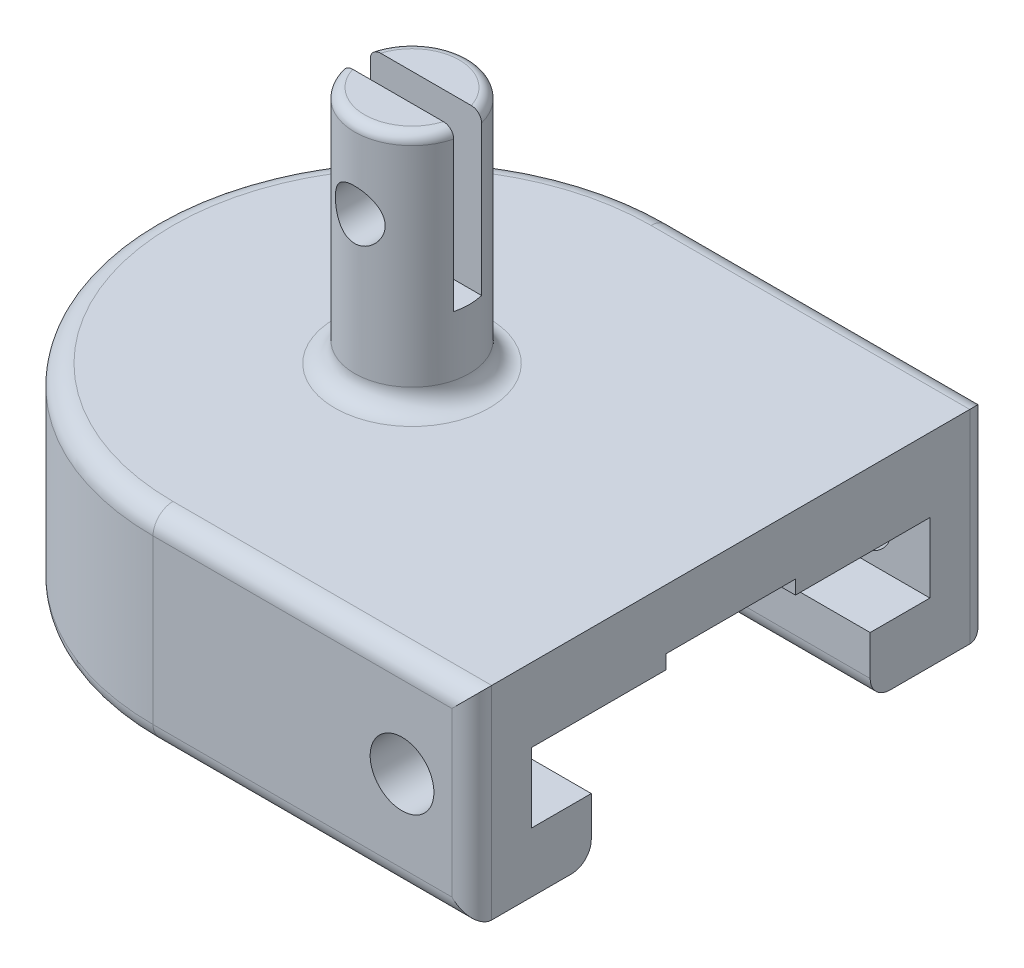
SolidWorks part; units mm, degrees
material "ABS"
ref_plane "Front Plane" through (0, 0, 0) normal (0, 0, 1) x (1, 0, 0)
ref_plane "Top Plane" through (0, 0, 0) normal (0, 1, 0) x (1, 0, 0)
ref_plane "Right Plane" through (0, 0, 0) normal (1, 0, 0) x (0, 0, -1)
sketch "Sketch1" plane through (0, 0, 0) normal (0, 1, 0) x (1, 0, 0)
  line L0 (0, 13) -> (16, 13)
  line L1 (0, -13) -> (16, -13)
  line L2 (0, 7) -> (16, 7)
  line L3 (16, 13) -> (16, 7)
  line L4 (0, -7) -> (16, -7)
  line L5 (16, -7) -> (16, -13)
  arc A0 (0, 7) -> (0, -7) centre (0, 0) ccw
  arc A1 (0, 13) -> (0, -13) centre (0, 0) ccw
  dimension "D1" = 6
  dimension "D2" = 7
  dimension "D3" = 16
  dimension "D4" = 16
extrude "Boss-Extrude1" add sketch "Sketch1" along normal blind 3
sketch "Sketch2" plane through (0, 3, 0) normal (0, 1, 0) x (1, 0, 0)
  line L0 (0, 13) -> (16, 13)
  line L1 (16, 13) -> (16, 10)
  line L2 (16, 7) -> (16, 13) construction
  line L3 (16, -13) -> (0, -13)
  line L4 (16, -13) -> (16, -10)
  line L7 (16, -13) -> (16, -7) construction
  line L8 (0, 10) -> (16, 10)
  line L9 (0, -10) -> (16, -10)
  arc A0 (0, 10) -> (0, -10) centre (0, 0) ccw
  arc A1 (0, 13) -> (0, -13) centre (0, 0) ccw
  dimension "D2" = 3
extrude "Boss-Extrude2" add sketch "Sketch2" along normal blind 3.5
sketch "Sketch3" plane through (0, 6.5, 0) normal (0, 1, 0) x (1, 0, 0)
  line L0 (16, 13) -> (0, 13)
  line L1 (16, 13) -> (16, 7)
  line L3 (0, -13) -> (16, -13)
  line L4 (16, -13) -> (16, -7)
  line L5 (16, -7) -> (0, -7) construction
  line L6 (16, -10) -> (16, -7) construction
  line L8 (16, 7) -> (16, -7)
  arc A1 (0, 13) -> (0, -13) centre (0, 0) ccw
extrude "Boss-Extrude3" add sketch "Sketch3" along normal blind 3.7
sketch "Sketch4" plane through (0, 10.2, 0) normal (0, 1, 0) x (1, 0, 0)
  circle A0 centre (0, 0) radius 2.88
  dimension "D1" = 5.76
extrude "Boss-Extrude4" add sketch "Sketch4" along normal blind 12
sketch "Sketch11" plane through (16, 0, 0) normal (1, 0, 0) x (0, 0, -1)
  line L5 (-10, 6.5) -> (10, 6.5) construction
  line L6 (-3.25, 6.5) -> (3.25, 6.5)
  line L7 (-3.25, 6.5) -> (-3.25, 7.2)
  line L8 (-3.25, 7.2) -> (3.25, 7.2)
  line L9 (3.25, 6.5) -> (3.25, 7.2)
  line L10 (0, 10.2) -> (0, 6.5) construction
  line L11 (-13, 10.2) -> (13, 10.2) construction
  line L12 (0, 7.2) -> (0, 6.5) construction
  dimension "D1" = 0.7
  dimension "D2" = 6.5
extrude "Cut-Extrude3" cut sketch "Sketch11" against normal blind 23
hole_wizard "Ø2.5mm Dowel Hole1" positions "3DSketch4" profile "Sketch7" hole size "Ø2.5" standard "ANSI Metric" end condition through all
sketch3d "3DSketch4"
  point P0 (-0.0024, 18.1049, 2.88)
  point P12 (-0.0024, 18.1049, 2.88)
sketch "Sketch7" plane through (-0.0024, 18.1049, 2.88) normal (0, 1, 0) x (1, 0, 0.0008)
  line L0 (0, 0) -> (0, 15.8935)
  line L1 (0, 15.8935) -> (1.25, 15.8935)
  line L2 (1.25, 15.8935) -> (1.25, 0)
  line L5 (1.25, 0) -> (0, 0)
  line L11 (0, -6.35) -> (0, 107.95) construction
  dimension "Thru Hole Dia." = 2.5
  dimension "Thru Hole Depth" = 15.8935
sketch "Sketch8" plane through (0, 0, 13) normal (0, 0, 1) x (1, 0, 0)
  line L0 (16, 5.1) -> (0, 5.1) construction
  line L1 (16, 10.2) -> (16, 0) construction
  line L2 (0, 10.2) -> (0, 0) construction
  circle A0 centre (12.5, 5.1) radius 1.6
  dimension "D1" = 3.2
  dimension "D2" = 3.5
extrude "Cut-Extrude1" cut sketch "Sketch8" against normal through all
fillet "Fillet1" radius 1 11 edges at (8, 10.2, -13) (-13, 10.2, 0) (8, 0, -13) (-13, 0, 0) (8, 10.2, 13) (16, 5.1, 13) (8, 0, 13) (8, 0, -7) (-7, 0, 0) (8, 0, 7) (16, 5.1, -13)
fillet "Fillet2" radius 1 1 edges at (0, 10.2, 2.88)
sketch "Sketch10" plane through (0, 22.2, 0) normal (0, 1, 0) x (1, 0, 0)
  line L0 (-2.7936, 0.7) -> (2.7936, 0.7)
  line L1 (-2.7936, -0.7) -> (2.7936, -0.7)
  line L2 (-2.88, 0) -> (2.88, 0) construction
  circle A0 centre (0, 0) radius 2.88 construction
  circle A1 centre (0, 0) radius 2.88 construction
  arc A2 (2.7936, -0.7) -> (2.7936, 0.7) centre (0, 0) ccw
  arc A3 (-2.7936, 0.7) -> (-2.7936, -0.7) centre (0, 0) ccw
  dimension "D2" = 0.7
  dimension "D3" = 0.7
extrude "Cut-Extrude2" cut sketch "Sketch10" against normal blind 8
fillet "Fillet3" radius 0.5 2 edges at (0, 22.2, -2.88) (0, 22.2, 2.88)
